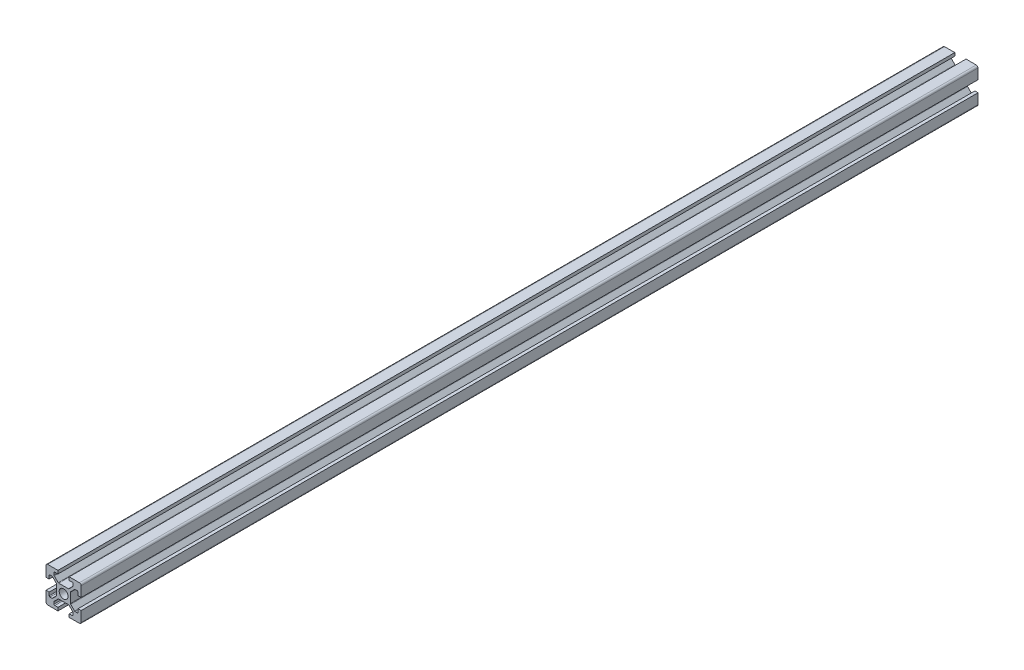
SolidWorks part; units mm, degrees
material "1060 Alloy"
ref_plane "Front Plane" through (0, 0, 0) normal (0, 0, 1) x (1, 0, 0)
ref_plane "Top Plane" through (0, 0, 0) normal (0, 1, 0) x (1, 0, 0)
ref_plane "Right Plane" through (0, 0, 0) normal (1, 0, 0) x (0, 0, -1)
sketch "Sketch1" plane through (0, 0, 0) normal (0, 0, 1) x (1, 0, 0)
  line L0 (20, 0) -> (-8.059, 28.059) construction
  line L1 (0, 0) -> (6.8, 0)
  line L2 (0, 0) -> (0, 6.8)
  line L3 (0, 20) -> (6.8, 20)
  line L4 (20, 0) -> (20, 6.8)
  line L5 (6.8, 20) -> (6.8, 18.2)
  line L6 (20, 20) -> (8.2322, 8.2322) construction
  line L7 (12.95, 6.1) -> (7.05, 6.1)
  line L8 (13.9, 7.05) -> (13.9, 12.95)
  line L9 (12.95, 13.9) -> (7.05, 13.9)
  line L10 (6.1, 7.05) -> (6.1, 12.95)
  line L11 (13.9, 6.1) -> (6.1, 13.9) construction
  line L12 (13.9, 13.9) -> (6.1, 6.1) construction
  line L13 (4.55, 16.4) -> (7.05, 13.9)
  line L14 (13.2, 18.2) -> (13.2, 20)
  line L15 (1.8, 6.8) -> (0, 6.8)
  line L16 (0, 13.2) -> (0, 20)
  line L17 (0, 13.2) -> (1.8, 13.2)
  line L18 (10, 10) -> (10, 13.9) construction
  line L19 (16.4, 4.55) -> (13.9, 7.05)
  line L20 (4.55, 16.4) -> (4.55, 18.2)
  line L21 (4.55, 18.2) -> (6.8, 18.2)
  line L22 (13.2, 18.2) -> (15.45, 18.2)
  line L23 (15.45, 18.2) -> (15.45, 16.4)
  line L24 (15.45, 16.4) -> (12.95, 13.9)
  line L25 (16.4, 4.55) -> (18.2, 4.55)
  line L26 (18.2, 4.55) -> (18.2, 6.8)
  line L27 (20, 6.8) -> (18.2, 6.8)
  line L28 (18.2, 13.2) -> (20, 13.2)
  line L29 (18.2, 13.2) -> (18.2, 15.45)
  line L30 (18.2, 15.45) -> (16.4, 15.45)
  line L31 (16.4, 15.45) -> (13.9, 12.95)
  line L32 (1.8, 4.55) -> (3.6, 4.55)
  line L33 (3.6, 15.45) -> (6.1, 12.95)
  line L34 (3.6, 15.45) -> (1.8, 15.45)
  line L35 (1.8, 15.45) -> (1.8, 13.2)
  line L36 (0, 13.2) -> (1.8, 13.2)
  line L37 (1.8, 6.8) -> (0, 6.8)
  line L38 (3.6, 4.55) -> (6.1, 7.05)
  line L39 (1.8, 6.8) -> (1.8, 4.55)
  line L40 (15.45, 3.6) -> (12.95, 6.1)
  line L41 (4.55, 3.6) -> (7.05, 6.1)
  line L42 (4.55, 1.8) -> (4.55, 3.6)
  line L43 (6.8, 1.8) -> (4.55, 1.8)
  line L44 (6.8, 1.8) -> (6.8, 0)
  line L45 (15.45, 3.6) -> (15.45, 1.8)
  line L46 (15.45, 1.8) -> (13.2, 1.8)
  line L47 (13.2, 0) -> (13.2, 1.8)
  line L48 (13.2, 20) -> (20, 20)
  line L49 (20, 13.2) -> (20, 20)
  line L50 (13.2, 0) -> (20, 0)
  line L51 (6.1, 6.1) -> (-5.5045, -5.5045) construction
  circle A0 centre (10, 10) radius 2.5
  point P25 (10, 16.4)
  point P39 (13.2, 19.1)
  point P46 (0.9, 6.8)
  dimension "D3" = 5
  dimension "D2" = 20
  dimension "D4" = 7.8
  dimension "D5" = 7.8
  dimension "D6" = 6.8
  dimension "D7" = 6.8
  dimension "D8" = 1.8
  dimension "D9" = 10.9
  dimension "D10" = 1.8
  dimension "D11" = 10.9
  dimension "D12" = 20
extrude "Boss-Extrude1" add sketch "Sketch1" along normal blind 510 contours L47 L50 L4 L27 L26 L25 L19 L8 L31 L30 L29 L28 L49 L48 L14 L22 L23 L24 L9 L13 L20 L21 L5 L3 L16 L17 L35 L34 L33 L10 L38 L32 L39 L15 L2 L1 L44 L43 L42 L41 L7 L40 L45 L46 A0 region at (0.2828, 3.4, 0)
fillet "Fillet1" radius 1 4 edges at (20, 20, 255) (20, 0, 255) (0, 0, 255) (0, 20, 255)
fillet "Fillet2" radius 0.5 6 edges at (4.55, 18.2, 255) (4.55, 16.4, 255) (7.05, 13.9, 255) (15.45, 18.2, 255) (15.45, 16.4, 255) (12.95, 13.9, 255)
fillet "Fillet3" radius 0.5 6 edges at (18.2, 15.45, 255) (16.4, 15.45, 255) (13.9, 12.95, 255) (18.2, 4.55, 255) (13.9, 7.05, 255) (16.4, 4.55, 255)
fillet "Fillet4" radius 0.5 6 edges at (1.8, 15.45, 255) (3.6, 15.45, 255) (6.1, 12.95, 255) (3.6, 4.55, 255) (1.8, 4.55, 255) (6.1, 7.05, 255)
fillet "Fillet5" radius 0.5 6 edges at (7.05, 6.1, 255) (4.55, 3.6, 255) (4.55, 1.8, 255) (15.45, 1.8, 255) (15.45, 3.6, 255) (12.95, 6.1, 255)
